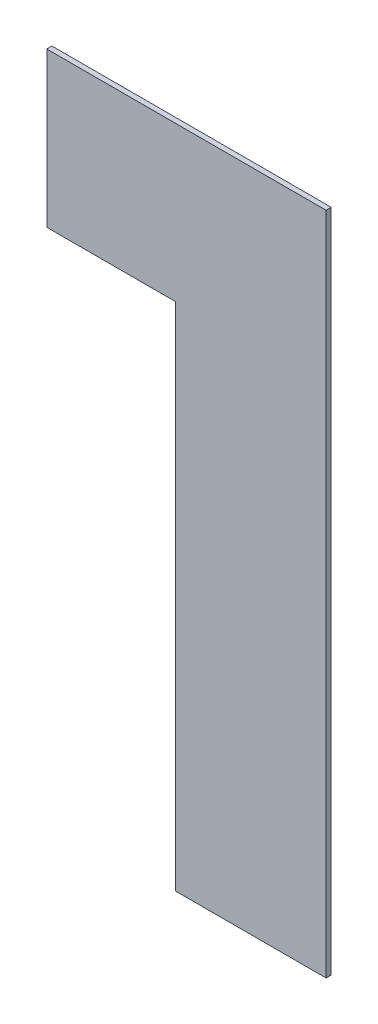
SolidWorks part; units mm, degrees
ref_plane "Ön Düzlem" through (0, 0, 0) normal (0, 0, 1) x (1, 0, 0)
ref_plane "Üst Düzlem" through (0, 0, 0) normal (0, 1, 0) x (1, 0, 0)
ref_plane "Sağ Düzlem" through (0, 0, 0) normal (1, 0, 0) x (0, 0, -1)
sketch "Çizim1" plane through (0, 0, 0) normal (0, 0, 1) x (1, 0, 0)
  line L0 (0, 0) -> (0, -900)
  line L1 (0, -900) -> (750, -900)
  line L2 (750, -900) -> (750, -2874)
  line L3 (750, -2874) -> (1628, -2874)
  line L4 (1628, -2874) -> (1628, 0)
  line L5 (1628, 0) -> (0, 0)
  dimension "D1" = 2874
  dimension "D2" = 878
  dimension "D3" = 900
  dimension "D4" = 750
  dimension "D5" = 1974
  dimension "D6" = 1628
base flange "Taban-Flanş1" sketch "Çizim1" thickness 30 reverse thickness direction no parameters "D1"=4
sketch "Çizim2" plane through (0, 0, 0) normal (0, 0, 1) x (1, 0, 0)
  line L0 (750, -2874) -> (1628, -2874) construction
  line L1 (750, -2874) -> (1090, -2874)
  line L2 (750, -2874) -> (750, -564)
  line L3 (750, -564) -> (1090, -564)
  line L4 (1090, -2874) -> (1090, -564)
  line L5 (750, -900) -> (750, -2874) construction
  line L6 (0, 0) -> (0, -900) construction
  line L7 (0, -900) -> (750, -900) construction
  line L8 (1628, 0) -> (0, 0) construction
  dimension "D1" = 340
  dimension "D2" = 2310
  dimension "D3" = 564
  dimension "D4" = 750
  dimension "D5" = 336
sketch "Çizim3" plane through (0, 0, 0) normal (0, 0, 1) x (1, 0, 0)
  line L0 (750, -900) -> (750, -2874) construction
  line L1 (1628, -2874) -> (750, -2874)
  line L2 (1628, -2874) -> (1628, -3875)
  line L3 (1628, -3875) -> (750, -3875)
  line L4 (750, -2874) -> (750, -3875)
  line L5 (1628, 0) -> (0, 0) construction
  dimension "D1" = 3875
base flange "Sekme1" sketch "Çizim3" thickness 30 reverse thickness direction no parameters "D1"=4
sketch "Çizim4" plane through (0, 0, 0) normal (0, 0, 1) x (1, 0, 0)
  line L0 (1628, -3875) -> (1628, 0) construction
  line L1 (750, -3875) -> (1060, -3875)
  line L2 (750, -3875) -> (750, -1365)
  line L3 (750, -1365) -> (1060, -1365)
  line L4 (1060, -3875) -> (1060, -1365)
  line L5 (0, -900) -> (750, -900) construction
  line L6 (0, 0) -> (0, -900) construction
  line L7 (1628, 0) -> (0, 0) construction
  point P13 (1628, 0)
  point P14 (0, 0)
  point P16 (0, -900)
  dimension "D1" = 2510
  dimension "D2" = 310
  dimension "D3" = 568
  dimension "D4" = 878
  dimension "D5" = 2975
  dimension "D6" = 750
  dimension "D7" = 3875
  dimension "D8" = 900
  dimension "D9" = 1628
sketch "Büküm-Çizgileri1" [suppressed] plane through (0, 0, 0) normal (0, 1, 0) x (1, 0, 0)
sketch "Sınırlandırma-Kutusu1" [suppressed] plane through (0, 0, 0) normal (0, 1, 0) x (1, 0, 0)
sheet metal parameters "Sac-Levha1" thickness 30 parameters "D1"=4
flat pattern "Düz-Çoğaltma1" [suppressed]
sketch "Büküm-Çizgileri2" plane through (0, 0, 0) normal (0, 1, 0) x (1, 0, 0)
sketch3d "Sınırlandırma-Kutusu2" [suppressed]
  line L0 (1628, 0, 0) -> (1628, -2874, 0) construction
  line L1 (0, 0, 0) -> (0, -2874, 0) construction
  line L2 (1628, 0, 0) -> (0, 0, 0) construction
  line L3 (1628, -2874, 0) -> (0, -2874, 0) construction
sheet metal parameters "Sac-Levha2" thickness 30 parameters "D1"=4
flat pattern "Düz-Çoğaltma2"
sketch "Büküm-Çizgileri3" plane through (0, 0, 0) normal (0, 1, 0) x (1, 0, 0)
sketch3d "Sınırlandırma-Kutusu3" [suppressed]
  line L0 (1628, 0, 0) -> (1628, -3875, 0) construction
  line L1 (0, 0, 0) -> (0, -3875, 0) construction
  line L2 (1628, 0, 0) -> (0, 0, 0) construction
  line L3 (1628, -3875, 0) -> (0, -3875, 0) construction
